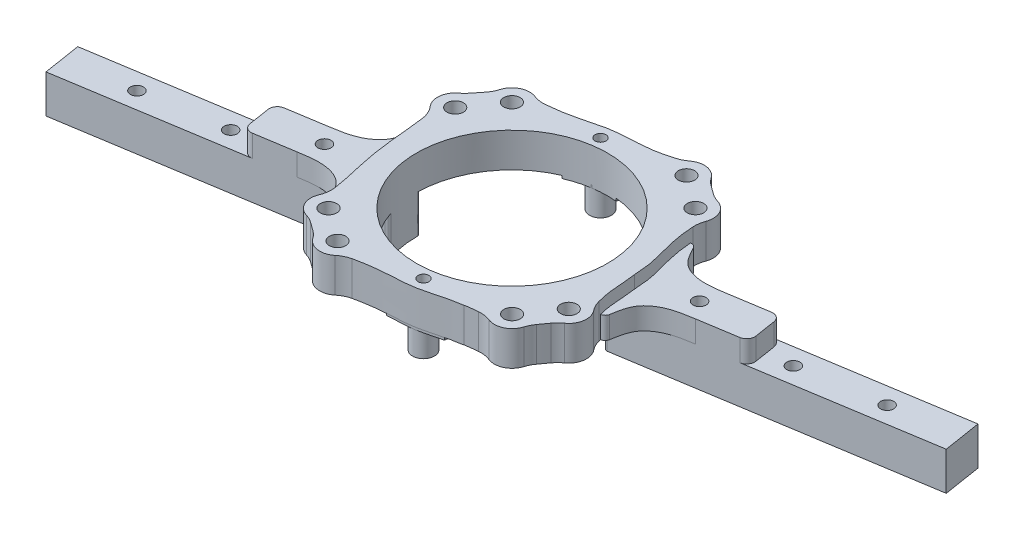
SolidWorks part; units mm, degrees
material "6061 合金"
ref_plane "前视基准面" through (0, 0, 0) normal (0, 0, 1) x (1, 0, 0)
ref_plane "上视基准面" through (0, 0, 0) normal (0, 1, 0) x (1, 0, 0)
ref_plane "右视基准面" through (0, 0, 0) normal (1, 0, 0) x (0, 0, -1)
sketch "草图1" plane through (0, 0, 0) normal (0, 1, 0) x (1, 0, 0)
  circle A0 centre (0, 0) radius 17.5
  circle A1 centre (0, 0) radius 18.901
  dimension "D1" = 35
extrude "凸台-拉伸1" add sketch "草图1" along normal blind 2
sketch "草图2" plane through (0, 0, 0) normal (0, -1, 0) x (1, 0, 0)
  circle A0 centre (-10.7739, 21.1656) radius 1.5
  circle A1 centre (16.8004, 16.7872) radius 1.5
  circle A2 centre (21.1656, 10.7739) radius 1.5
  circle A3 centre (16.7872, -16.8004) radius 1.5
  circle A4 centre (10.7739, -21.1656) radius 1.5
  circle A5 centre (-16.8004, -16.7872) radius 1.5
  circle A6 centre (-21.1656, -10.7739) radius 1.5
  circle A7 centre (-16.7872, 16.8004) radius 1.5
  circle A28 centre (0, 0) radius 17.5
  spline S3 degree 3 poles (11.007, 19.7796) (11.3114, 19.6784) (14.2307, 19.3249) (16.1426, 19.3879) (17.8124, 19.1708) (19.4344, 17.903) (21.2548, 15.4236) (23.0457, 12.9332) (23.7495, 10.9887) (23.274, 8.5261) (21.9734, 4.7628) (22.0269, 1.1873) (21.7447, -0.683) knots 0 0 0 0 0.101498 0.202996 0.236379 0.269761 0.41266 0.555558 0.58894 0.622323 0.811161 1 1 1 1
  spline S4 degree 3 poles (21.7447, -0.683) (21.6068, -1.5972) (21.6068, -3.3452) (20.6875, -6.8867) (19.4907, -11.3034) (19.4854, -15.3123) (19.178, -17.8032) (17.9056, -19.4334) (15.4365, -21.2528) (12.9718, -22.9922) (11.1783, -23.6905) (8.6855, -23.5473) (4.924, -21.9674) (0.2192, -21.8124) (-3.3386, -21.5662) (-6.4463, -20.811) (-9.0785, -20.0902) (-12.7412, -19.485) (-15.1247, -19.3735) (-17.5839, -19.2481) (-19.3895, -18.0994) (-21.0348, -15.4072) (-24.0166, -12.4025) (-22.9927, -9.5882) (-22.6062, -7.2218) (-22.137, -3.99) (-21.8105, 0.6983) (-20.6859, 7.8895) (-19.0439, 13.1272) (-19.2816, 16.8284) knots 0 0 0 0 0.028865 0.055245 0.115073 0.172417 0.182554 0.192692 0.236085 0.279479 0.287719 0.295959 0.357153 0.414497 0.443362 0.469742 0.515309 0.529597 0.586941 0.590792 0.607069 0.650462 0.693856 0.724941 0.736674 0.770353 0.827697 0.885312 1 1 1 1
  spline S5 degree 3 poles (-19.2816, 16.8284) (-19.323, 17.5174) (-18.1907, 19.2578) (-15.4061, 21.2421) (-12.9273, 23.0421) (-10.9838, 23.7431) (-9.3566, 23.4387) (-7.2233, 22.7077) (-4.4614, 22.2162) (-1.8337, 21.8607) (0.7732, 21.7432) (3.3794, 21.5754) (7.3403, 20.5662) (8.6858, 20.19) (9.8558, 19.9936) (10.7406, 19.8682) (11.007, 19.7796) knots 0 0 0 0 0.047987 0.150696 0.253406 0.277399 0.301393 0.374345 0.447298 0.510152 0.573007 0.641327 0.709648 0.853023 0.882058 1 1 1 1
  dimension "D1" = 3
extrude "凸台-拉伸2" add sketch "草图2" along normal blind 4.3 and the other way blind 2
sketch "草图3" plane through (0, -4.3, 0) normal (0, -1, 0) x (1, 0, 0)
  line L0 (8.0513, 9.3531) -> (-43.8768, 17.5986) construction
  line L1 (3.0581, 19.2587) -> (0, 0) construction
  line L2 (0, 0) -> (-3.0579, -19.2577) construction
  line L3 (-8.1547, -9.3357) -> (43.7734, -17.5812) construction
  circle A0 centre (3.0581, 19.2587) radius 2
  circle A1 centre (3.0581, 19.2587) radius 9 construction
  circle A2 centre (-3.0579, -19.2577) radius 2
  circle A3 centre (-3.0579, -19.2577) radius 9 construction
  dimension "D1" = 18
  dimension "D2" = 4
  dimension "D3" = 18
  dimension "D4" = 4
extrude "凸台-拉伸3" add sketch "草图3" along normal blind 5
sketch "草图5" plane through (0, -4.3, 0) normal (0, -1, 0) x (1, 0, 0)
  line L0 (0, 0) -> (38.9853, -6.1904) construction
  line L1 (70.6703, -14.0546) -> (-71.5479, 8.5279) construction
  circle A0 centre (3.0581, 19.2587) radius 5 construction
  arc A1 (-1.5944, 17.4272) -> (6.9144, 16.0761) centre (0, 0) cw
  arc A2 (-2.6852, -17.2928) -> (2.7444, 17.2835) centre (0, 0) ccw construction
  arc A3 (-1.3158, 21.6815) -> (-1.5944, 17.4272) centre (3.0581, 19.2587) ccw
  arc A4 (7.9454, 20.3141) -> (6.9144, 16.0761) centre (3.0581, 19.2587) cw
  arc A5 (-7.9672, -20.2075) -> (-6.9144, -16.0761) centre (-3.0581, -19.2587) cw
  arc A6 (-6.9144, -16.0761) -> (1.5944, -17.4272) centre (0, 0) ccw
  arc A7 (1.262, -21.7761) -> (1.5944, -17.4272) centre (-3.0581, -19.2587) ccw
  spline S0 degree 3 poles (-1.3158, 21.6815) (-0.2135, 21.5939) (1.3807, 21.5885) (3.4585, 21.3907) (5.444, 20.9684) (6.9168, 20.5202) (7.9454, 20.3141) knots 0 0 0 0 0.352817 0.508743 0.665414 1 1 1 1
  spline S2 degree 3 poles (-7.9672, -20.2075) (-6.892, -20.4656) (-5.3746, -20.9543) (-3.3377, -21.4099) (-1.319, -21.6234) (0.2201, -21.6535) (1.262, -21.7761) knots 0 0 0 0 0.352817 0.508743 0.665414 1 1 1 1
  dimension "D1" = 10
extrude "凸台-拉伸5" add sketch "草图5" along normal blind 0.5
sketch "草图6" plane through (0, -4.3, 0) normal (0, -1, 0) x (1, 0, 0)
  line L0 (0, 0) -> (83.2876, -13.2251) construction
  line L1 (70.6703, -14.0546) -> (-71.5479, 8.5279) construction
  line L2 (0, 0) -> (7.0837, 44.6111) construction
  line L3 (22.6545, 6.4264) -> (16.7134, 7.3698)
  line L4 (32.0065, -1.5404) -> (39.048, -2.6585)
  line L5 (71.6577, -7.8366) -> (-70.5606, 14.746) construction
  line L6 (-30.9094, 8.4499) -> (-37.9509, 9.5679)
  line L7 (40.2942, -4.3752) -> (39.9809, -6.3485)
  line L8 (19.5496, -13.1279) -> (13.6084, -12.1845)
  line L9 (30.9094, -8.4499) -> (37.9509, -9.5679)
  line L10 (39.6675, -8.3217) -> (39.9809, -6.3485)
  line L11 (-39.6675, 8.3217) -> (-39.9809, 6.3485)
  line L12 (-40.2942, 4.3752) -> (-39.9809, 6.3485)
  line L13 (-32.0065, 1.5404) -> (-39.048, 2.6585)
  line L14 (-19.5496, 13.1279) -> (-13.6084, 12.1845)
  line L15 (-22.6545, -6.4264) -> (-16.7134, -7.3698)
  circle A0 centre (21.1656, 10.7739) radius 2.5 construction
  arc A1 (1.5944, -17.4272) -> (6.9144, 16.0761) centre (0, 0) ccw construction
  arc A2 (13.3066, -11.3659) -> (16.1729, 6.685) centre (0, 0) ccw
  arc A3 (23.4842, 5.6027) -> (22.6545, 6.4264) centre (22.4977, 5.4388) ccw
  arc A4 (16.7134, 7.3698) -> (16.1729, 6.685) centre (16.6349, 6.876) ccw
  arc A5 (39.048, -2.6585) -> (40.2942, -4.3752) centre (38.8128, -4.14) cw
  arc A6 (13.6084, -12.1845) -> (13.3066, -11.3659) centre (13.6868, -11.6907) cw
  arc A7 (20.5935, -12.6017) -> (19.5496, -13.1279) centre (19.7064, -12.1402) cw
  arc A8 (37.9509, -9.5679) -> (39.6675, -8.3217) centre (38.1861, -8.0865) ccw
  arc A9 (-37.9509, 9.5679) -> (-39.6675, 8.3217) centre (-38.1861, 8.0865) ccw
  arc A10 (-39.048, 2.6585) -> (-40.2942, 4.3752) centre (-38.8128, 4.14) cw
  arc A11 (-20.5935, 12.6017) -> (-19.5496, 13.1279) centre (-19.7064, 12.1402) cw
  arc A12 (-13.6084, 12.1845) -> (-13.3066, 11.3659) centre (-13.6868, 11.6907) cw
  arc A13 (-16.1729, -6.685) -> (-13.3066, 11.3659) centre (0, 0) cw
  arc A14 (-16.7134, -7.3698) -> (-16.1729, -6.685) centre (-16.6349, -6.876) ccw
  arc A15 (-23.4842, -5.6027) -> (-22.6545, -6.4264) centre (-22.6575, -5.5997) ccw
  spline S0 degree 3 poles (20.5935, -12.6017) (20.8165, -12.1731) (21.4171, -11.0059) (22.8603, -8.9685) (26.5188, -7.7575) (29.1956, -8.1777) (30.9094, -8.4499) knots 0.057026 0.057026 0.057026 0.057026 0.169435 0.36028 0.616457 1 1 1 1
  spline S1 degree 3 poles (23.4842, 5.6027) (23.5634, 5.1261) (23.7729, 3.8302) (24.514, 1.446) (27.6174, -0.8387) (30.2927, -1.2683) (32.0065, -1.5404) knots 0.057026 0.057026 0.057026 0.057026 0.169435 0.36028 0.616457 1 1 1 1
  spline S2 degree 3 poles (-23.4842, -5.6027) (-23.5634, -5.1261) (-23.7729, -3.8302) (-24.514, -1.446) (-27.6174, 0.8387) (-30.2927, 1.2683) (-32.0065, 1.5404) knots 0.057026 0.057026 0.057026 0.057026 0.169435 0.36028 0.616457 1 1 1 1
  spline S3 degree 3 poles (-20.5935, 12.6017) (-20.8165, 12.1731) (-21.4171, 11.0059) (-22.8603, 8.9685) (-26.5188, 7.7575) (-29.1956, 8.1777) (-30.9094, 8.4499) knots 0.057026 0.057026 0.057026 0.057026 0.169435 0.36028 0.616457 1 1 1 1
  point P34 (15.8047, 7.514)
  dimension "D1" = 5
  dimension "D2" = 1
  dimension "D3" = 0.5
  dimension "D4" = 1.5
extrude "凸台-拉伸6" add sketch "草图6" against normal blind 4 separate body
sketch "草图7" plane through (0, -4.3, 0) normal (0, -1, 0) x (1, 0, 0)
  line L0 (17.2287, -6.2775) -> (70.5606, -14.746)
  line L1 (17.2287, -6.2775) -> (18.3258, 0.6319) construction
  line L2 (70.5606, -14.746) -> (71.6577, -7.8366)
  line L3 (18.3258, 0.6319) -> (71.6577, -7.8366)
  line L4 (17.2287, -6.2775) -> (71.6577, -7.8366) construction
  line L5 (70.5606, -14.746) -> (18.3258, 0.6319) construction
  line L6 (71.6577, -7.8366) -> (-70.5606, 14.746) construction
  line L7 (71.6266, -8.0321) -> (70.5916, -14.5504) construction
  line L8 (18.3258, 0.6319) -> (18.0775, 0.6713)
  line L9 (17.2287, -6.2775) -> (16.9804, -6.2381)
  line L10 (70.5606, -14.746) -> (-71.6577, 7.8366) construction
  line L11 (0, 0) -> (5.947, 37.4527) construction
  line L12 (-71.6577, 7.8366) -> (-70.5606, 14.746)
  line L13 (-17.2287, 6.2775) -> (-70.5606, 14.746)
  line L14 (-18.3258, -0.6319) -> (-71.6577, 7.8366)
  line L15 (-18.3258, -0.6319) -> (-18.0775, -0.6713)
  line L16 (-17.2287, 6.2775) -> (-16.9804, 6.2381)
  arc A0 (1.5944, -17.4272) -> (6.9144, 16.0761) centre (0, 0) ccw construction
  arc A1 (17.4991, 0.1726) -> (16.585, -5.5847) centre (0, 0) cw
  arc A2 (16.9804, -6.2381) -> (16.585, -5.5847) centre (17.0588, -5.7443) cw
  arc A3 (18.0775, 0.6713) -> (17.4991, 0.1726) centre (17.9991, 0.1775) ccw
  arc A4 (-18.0775, -0.6713) -> (-17.4991, -0.1726) centre (-17.9991, -0.1775) ccw
  arc A5 (-16.9804, 6.2381) -> (-16.585, 5.5847) centre (-17.0588, 5.7443) cw
  arc A6 (-16.585, 5.5847) -> (-17.4991, -0.1726) centre (0, 0) ccw
  point P1 (44.4432, -7.057)
  point P20 (16.3861, -6.1437)
  point P23 (17.4832, 0.7657)
  dimension "D1" = 0.5
extrude "凸台-拉伸7" add sketch "草图7" along normal blind 7
sketch "草图8" plane through (0, -11.3, 0) normal (0, -1, 0) x (1, 0, 0)
  circle A0 centre (59.2576, -9.4094) radius 1.2
  circle A1 centre (44.4432, -7.057) radius 1.2
  circle A2 centre (29.6288, -4.7047) radius 1.2
  circle A3 centre (-29.6288, 4.7047) radius 1.2
  circle A4 centre (-44.4432, 7.057) radius 1.2
  circle A5 centre (-59.2576, 9.4094) radius 1.2
  dimension "D1" = 2.4
extrude "切除-拉伸1" cut sketch "草图8" against normal through all
sketch "草图9" plane through (0, -4.3, 0) normal (0, -1, 0) x (1, 0, 0)
  circle A0 centre (16.8004, 16.7872) radius 3.25
  circle A1 centre (21.1656, 10.7739) radius 3.25
  circle A2 centre (16.7872, -16.8004) radius 3.25
  circle A3 centre (10.7739, -21.1656) radius 3.25
  circle A4 centre (-16.8004, -16.7872) radius 3.25
  circle A5 centre (-21.1656, -10.7739) radius 3.25
  circle A7 centre (-10.7739, 21.1656) radius 3.25
  circle A8 centre (-16.7872, 16.8004) radius 3.25
  circle A9 centre (-10.7739, 21.1656) radius 1.5
  circle A10 centre (-16.7872, 16.8004) radius 1.5
  circle A11 centre (-21.1656, -10.7739) radius 1.5
  circle A12 centre (-16.8004, -16.7872) radius 1.5
  circle A13 centre (10.7739, -21.1656) radius 1.5
  circle A15 centre (16.7872, -16.8004) radius 1.5
  circle A16 centre (21.1656, 10.7739) radius 1.5
  circle A17 centre (16.8004, 16.7872) radius 1.5
  dimension "D1" = 6.5
extrude "凸台-拉伸8" add sketch "草图9" against normal up to surface (6.3 mm away) up to face at (0, 2, 17.5)
chamfer "倒角1" distance 1.55 angle 45 8 edges at (-21.1656, -4.3, -12.2739) (-16.8004, -4.3, -18.2872) (10.7739, -4.3, -22.6656) (16.7872, -4.3, -18.3004) (21.1656, -4.3, 9.2739) (16.8004, -4.3, 15.2872) (-16.7872, -4.3, 15.3004) (-10.7739, -4.3, 19.6656)
fillet "圆角1" radius 5 16 edges at (17.0173, -1.15, -20.0422) (19.4426, -1.15, -14.9265) (8.2681, -1.15, -23.2352) (13.7915, -1.15, -22.3726) (-20.0444, -1.15, -16.9851) (-14.857, -1.15, -19.3921) (-22.722, -1.15, -7.9209) (-22.6228, -1.15, -13.679) (-19.2801, -1.15, 14.7152) (-17.0223, -1.15, 20.0419) (-8.1142, -1.15, 23.0333) (-13.7917, -1.15, 22.3723) (20.0425, -1.15, 17.0141) (14.8431, -1.15, 19.3817) (23.0958, -1.15, 8.1592) (22.3884, -1.15, 13.7851)
sketch "草图10" plane through (0, -9.3, 0) normal (0, -1, 0) x (1, 0, 0)
  circle A0 centre (3.0581, 19.2587) radius 1
  circle A1 centre (-3.0579, -19.2577) radius 1
  dimension "D1" = 2
extrude "切除-拉伸2" cut sketch "草图10" against normal through all
